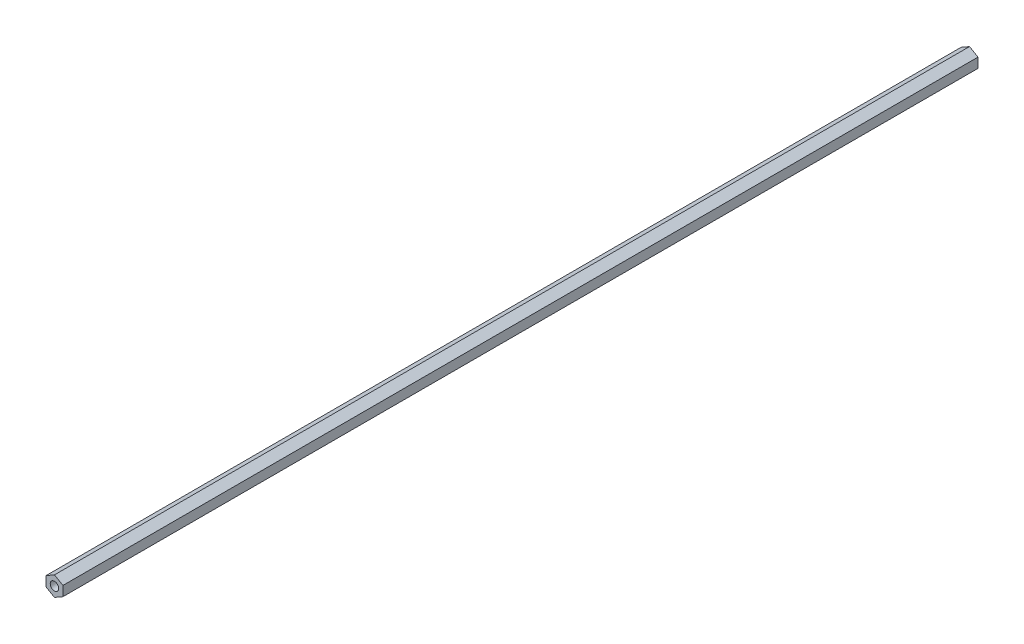
SolidWorks part; units mm, degrees
material "AISI 1020 Steel, Cold Rolled"
ref_plane "Front Plane" through (0, 0, 0) normal (0, 0, 1) x (1, 0, 0)
ref_plane "Top Plane" through (0, 0, 0) normal (0, 1, 0) x (1, 0, 0)
ref_plane "Right Plane" through (0, 0, 0) normal (1, 0, 0) x (0, 0, -1)
sketch "Sketch1" plane through (0, 0, 0) normal (0, 0, 1) x (1, 0, 0)
  line L1 (0, 7.3323) -> (-6.35, 3.6662) construction
  line L2 (-6.35, 3.6662) -> (-6.35, -3.6662) construction
  line L3 (-6.35, -3.6662) -> (0, -7.3323) construction
  line L4 (0, -7.3323) -> (6.35, -3.6662) construction
  line L5 (6.35, -3.6662) -> (6.35, 3.6662) construction
  line L6 (6.35, 3.6662) -> (0, 7.3323) construction
  circle A2 centre (0, 0) radius 6.35 construction
  dimension "Width" = 12.7
sketch "Sketch2" plane through (0, 0, 0) normal (1, 0, 0) x (0, 0, -1)
  line L0 (-342.9, 7.3323) -> (342.9, 7.3323) construction
  point P2 (0, 7.3323)
  point P3 (311.15, 7.3323)
  point P4 (-311.15, 7.3323)
  dimension "Length" = 685.8
  dimension "D2" = 31.75
  dimension "D1" = 31.75
sketch "Sketch3" plane through (0, 0, 0) normal (0, 0, 1) x (1, 0, 0)
  line L0 (-6.35, -3.6662) -> (0, -7.3323) construction
  line L1 (0, -7.3323) -> (6.35, -3.6662) construction
  line L2 (6.35, -3.6662) -> (6.35, 3.6662) construction
  line L3 (6.35, 3.6662) -> (0, 7.3323) construction
  line L4 (0, 7.3323) -> (-6.35, 3.6662) construction
  line L5 (-6.35, 3.6662) -> (-6.35, -3.6662) construction
  line L6 (-6.35, -3.6662) -> (0, -7.3323)
  line L7 (0, -7.3323) -> (6.35, -3.6662)
  line L8 (6.35, -3.6662) -> (6.35, 3.6662)
  line L9 (6.35, 3.6662) -> (0, 7.3323)
  line L10 (0, 7.3323) -> (-6.35, 3.6662)
  line L11 (-6.35, 3.6662) -> (-6.35, -3.6662)
extrude "Boss-Extrude2" add sketch "Sketch3" along normal up to vertex (342.9 mm away) and the other way up to vertex (342.9 mm away) up to point (0, 7.3323, 342.9) other way up to point (0, 7.3323, -342.9)
sketch "Sketch4" plane through (0, 0, 342.9) normal (0, 0, 1) x (1, 0, 0)
  point P0 (0, 0)
hole_wizard "1/4 (0.25) Diameter Hole1" positions "Sketch5" profile "Sketch6" hole size "1/4" standard "ANSI Inch"
sketch "Sketch5" plane through (0, 0, 342.9) normal (0, 0, 1) x (1, 0, 0)
  point P0 (0, 0)
sketch "Sketch6" plane through (0, 0, 342.9) normal (1, 0, 0) x (0, -1, 0)
  line L0 (0, 0) -> (0, 27.3077)
  line L1 (0, 27.3077) -> (3.175, 25.4)
  line L2 (3.175, 25.4) -> (3.175, 0)
  line L5 (3.175, 0) -> (0, 0)
  line L10 (0, 27.3077) -> (-3.175, 25.4) construction
  line L11 (0, -6.35) -> (0, 107.95) construction
  dimension "Hole Dia." = 6.35
  dimension "Hole Depth" = 25.4
  dimension "Drill Angle" = 118
hole_wizard "1/4 (0.25) Diameter Hole2" positions "Sketch7" profile "Sketch8" hole size "1/4" standard "ANSI Inch"
sketch "Sketch7" plane through (0, 0, -342.9) normal (0, 0, -1) x (-1, 0, 0)
  point P0 (0, 0)
sketch "Sketch8" plane through (0, 0, -342.9) normal (1, 0, 0) x (0, 1, 0)
  line L0 (0, 0) -> (0, 27.3077)
  line L1 (0, 27.3077) -> (3.175, 25.4)
  line L2 (3.175, 25.4) -> (3.175, 0)
  line L5 (3.175, 0) -> (0, 0)
  line L10 (0, 27.3077) -> (-3.175, 25.4) construction
  line L11 (0, -6.35) -> (0, 107.95) construction
  dimension "Hole Dia." = 6.35
  dimension "Hole Depth" = 25.4
  dimension "Drill Angle" = 118
equation "\"D2@Sketch2\" = \"D1@Sketch2\""
equation "\"D1@Sketch2\" = \"Width@Sketch1\" * 2.5"
